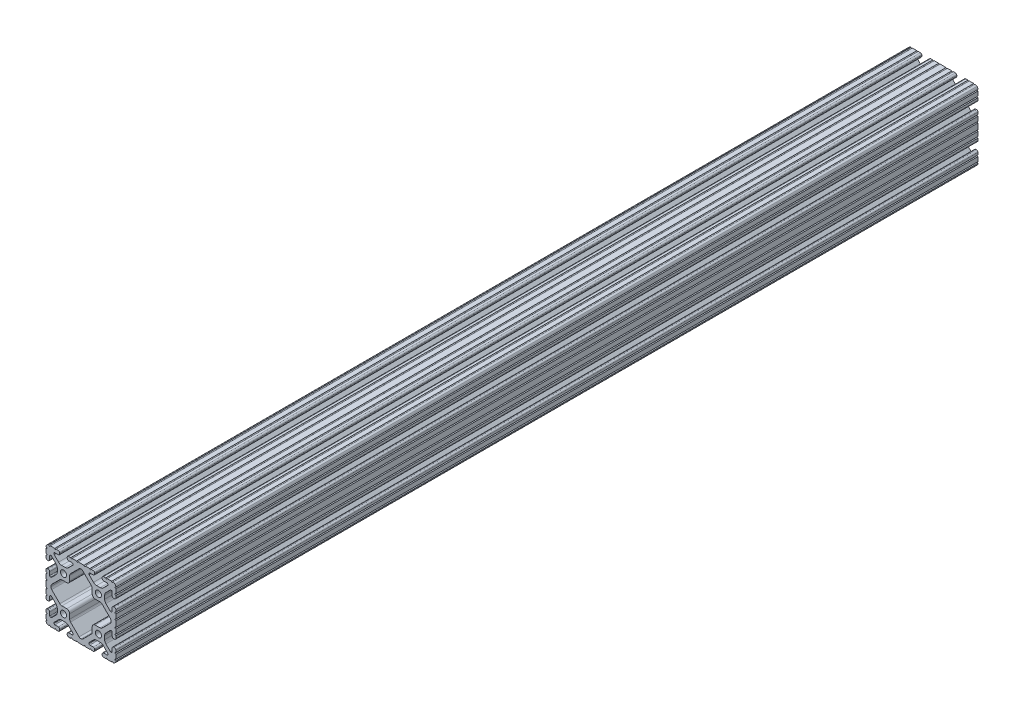
SolidWorks part; units mm, degrees
ref_plane "Front Plane" through (0, 0, 0) normal (0, 0, 1) x (1, 0, 0)
ref_plane "Top Plane" through (0, 0, 0) normal (0, 1, 0) x (1, 0, 0)
ref_plane "Right Plane" through (0, 0, 0) normal (1, 0, 0) x (0, 0, -1)
sketch "Sketch1" plane through (0, 0, 0) normal (0, 0, 1) x (1, 0, 0)
  line L0 (0, 38.1) -> (0, -38.1) construction
  line L1 (-38.1, -38.1) -> (38.1, -38.1) construction
  line L2 (-38.1, -38.1) -> (-38.1, 38.1) construction
  line L3 (-38.1, 38.1) -> (38.1, 38.1) construction
  line L4 (38.1, -38.1) -> (38.1, 38.1) construction
  line L5 (0, 38.1) -> (0, -38.1) construction
  line L6 (-38.1, 0) -> (38.1, 0) construction
  line L7 (-19.05, 19.05) -> (19.05, 19.05) construction
  line L8 (-19.05, 19.05) -> (-19.05, -19.05) construction
  line L9 (-19.05, -19.05) -> (19.05, -19.05) construction
  line L10 (19.05, 19.05) -> (19.05, -19.05) construction
  line L11 (-23.114, 38.1) -> (-23.114, -38.1) construction
  line L12 (-23.114, -38.1) -> (-14.986, 38.1) construction
  line L13 (-14.986, 38.1) -> (-14.986, -38.1) construction
  circle A0 centre (19.05, 19.05) radius 3.3274
  point P0 (0, 0)
  point P9 (0, 0)
  point P12 (-19.05, 0)
  line B0 (-11.3637, -22.8433) -> (-2.0515, -32.1555)
  line B1 (-12.2936, -15.4686) -> (-12.2936, -20.5983)
  line B2 (-20.769, -12.2936) -> (-15.4686, -12.2936)
  line B3 (-31.9021, -2.4756) -> (-23.0141, -11.3637)
  line B4 (-23.0141, 11.3637) -> (-31.9021, 2.4756)
  line B5 (-15.4686, 12.2936) -> (-20.769, 12.2936)
  line B6 (-12.2936, 20.5983) -> (-12.2936, 15.4686)
  line B7 (-2.0515, 32.1555) -> (-11.3637, 22.8433)
  line B8 (11.3637, 22.8433) -> (2.0515, 32.1555)
  line B9 (12.2936, 15.4686) -> (12.2936, 20.5983)
  line B10 (20.769, 12.2936) -> (15.4686, 12.2936)
  line B11 (31.9021, 2.4756) -> (23.0141, 11.3637)
  line B12 (23.0141, -11.3637) -> (31.9021, -2.4756)
  line B13 (15.4686, -12.2936) -> (20.769, -12.2936)
  line B14 (12.2936, -20.5983) -> (12.2936, -15.4686)
  line B15 (2.0515, -32.1555) -> (11.3637, -22.8433)
  line B16 (-4.7773, 38.1) -> (-9.6053, 38.1)
  line B17 (-11.1289, 38.1) -> (-13.4112, 38.1)
  line B18 (-14.986, 36.5252) -> (-14.986, 35.6108)
  line B19 (-13.4112, 34.036) -> (-9.652, 34.036)
  line B20 (-8.763, 33.147) -> (-8.763, 32.4935)
  line B21 (-9.0234, 31.8649) -> (-13.6907, 27.1976)
  line B22 (-17.0493, 25.8064) -> (-21.0507, 25.8064)
  line B23 (-24.4093, 27.1976) -> (-29.1002, 31.8885)
  line B24 (-29.337, 32.7207) -> (-29.337, 33.147)
  line B25 (-28.448, 34.036) -> (-24.6888, 34.036)
  line B26 (-23.114, 35.6108) -> (-23.114, 36.5252)
  line B27 (-24.6888, 38.1) -> (-27.0772, 38.1)
  line B28 (-28.6011, 38.1) -> (-33.4288, 38.1)
  line B29 (-38.1, 33.373) -> (-38.1, 28.5453)
  line B30 (-38.1, 27.0238) -> (-38.1, 24.6302)
  line B31 (-36.5252, 23.0554) -> (-35.6108, 23.0554)
  line B32 (-34.036, 24.6302) -> (-34.036, 28.448)
  line B33 (-33.147, 29.337) -> (-32.6643, 29.337)
  line B34 (-32.0357, 29.0766) -> (-27.1976, 24.2385)
  line B35 (-25.8064, 20.8799) -> (-25.8064, 17.2201)
  line B36 (-27.1976, 13.8615) -> (-31.9489, 9.1101)
  line B37 (-32.7869, 8.763) -> (-33.0603, 8.763)
  line B38 (-34.036, 9.7387) -> (-34.036, 13.4698)
  line B39 (-35.6108, 15.0446) -> (-36.5252, 15.0446)
  line B40 (-38.1, 13.4698) -> (-38.1, 11.075)
  line B41 (-38.1, 9.552) -> (-38.1, 4.7238)
  line B42 (-38.1, 3.2007) -> (-38.1, -3.2007)
  line B43 (-38.1, -4.7238) -> (-38.1, -9.552)
  line B44 (-38.1, -11.075) -> (-38.1, -13.4698)
  line B45 (-36.5252, -15.0446) -> (-35.6108, -15.0446)
  line B46 (-34.036, -13.4698) -> (-34.036, -9.7387)
  line B47 (-33.0603, -8.763) -> (-32.7869, -8.763)
  line B48 (-31.9489, -9.1101) -> (-27.1976, -13.8615)
  line B49 (-25.8064, -17.2201) -> (-25.8064, -20.8799)
  line B50 (-27.1976, -24.2385) -> (-32.0357, -29.0766)
  line B51 (-32.6643, -29.337) -> (-33.147, -29.337)
  line B52 (-34.036, -28.448) -> (-34.036, -24.6302)
  line B53 (-35.6108, -23.0554) -> (-36.5252, -23.0554)
  line B54 (-38.1, -24.6302) -> (-38.1, -27.0238)
  line B55 (-38.1, -28.5453) -> (-38.1, -33.373)
  line B56 (-33.4288, -38.1) -> (-28.6011, -38.1)
  line B57 (-27.0772, -38.1) -> (-24.6888, -38.1)
  line B58 (-23.114, -36.5252) -> (-23.114, -35.6108)
  line B59 (-24.6888, -34.036) -> (-28.448, -34.036)
  line B60 (-29.337, -33.147) -> (-29.337, -32.7207)
  line B61 (-29.1002, -31.8885) -> (-24.4093, -27.1976)
  line B62 (-21.0507, -25.8064) -> (-17.0493, -25.8064)
  line B63 (-13.6907, -27.1976) -> (-9.0234, -31.8649)
  line B64 (-8.763, -32.4935) -> (-8.763, -33.147)
  line B65 (-9.652, -34.036) -> (-13.4112, -34.036)
  line B66 (-14.986, -35.6108) -> (-14.986, -36.5252)
  line B67 (-13.4112, -38.1) -> (-11.1289, -38.1)
  line B68 (-9.6053, -38.1) -> (-4.7773, -38.1)
  line B69 (-3.2537, -38.1) -> (3.2537, -38.1)
  line B70 (4.7773, -38.1) -> (9.6053, -38.1)
  line B71 (11.1289, -38.1) -> (13.4112, -38.1)
  line B72 (14.986, -36.5252) -> (14.986, -35.6108)
  line B73 (13.4112, -34.036) -> (9.652, -34.036)
  line B74 (8.763, -33.147) -> (8.763, -32.4935)
  line B75 (9.0234, -31.8649) -> (13.6907, -27.1976)
  line B76 (17.0493, -25.8064) -> (21.0507, -25.8064)
  line B77 (24.4093, -27.1976) -> (29.1002, -31.8885)
  line B78 (29.337, -32.7207) -> (29.337, -33.147)
  line B79 (28.448, -34.036) -> (24.6888, -34.036)
  line B80 (23.114, -35.6108) -> (23.114, -36.5252)
  line B81 (24.6888, -38.1) -> (27.0772, -38.1)
  line B82 (28.6011, -38.1) -> (33.4288, -38.1)
  line B83 (38.1, -33.373) -> (38.1, -28.5453)
  line B84 (38.1, -27.0238) -> (38.1, -24.6302)
  line B85 (36.5252, -23.0554) -> (35.6108, -23.0554)
  line B86 (34.036, -24.6302) -> (34.036, -28.448)
  line B87 (33.147, -29.337) -> (32.6643, -29.337)
  line B88 (32.0357, -29.0766) -> (27.1976, -24.2385)
  line B89 (25.8064, -20.8799) -> (25.8064, -17.2201)
  line B90 (27.1976, -13.8615) -> (31.9489, -9.1101)
  line B91 (32.7869, -8.763) -> (33.0603, -8.763)
  line B92 (34.036, -9.7387) -> (34.036, -13.4698)
  line B93 (35.6108, -15.0446) -> (36.5252, -15.0446)
  line B94 (38.1, -13.4698) -> (38.1, -11.075)
  line B95 (38.1, -9.552) -> (38.1, -4.7238)
  line B96 (38.1, -3.2007) -> (38.1, 3.2007)
  line B97 (38.1, 4.7238) -> (38.1, 9.552)
  line B98 (38.1, 11.075) -> (38.1, 13.4698)
  line B99 (36.5252, 15.0446) -> (35.6108, 15.0446)
  line B100 (34.036, 13.4698) -> (34.036, 9.7387)
  line B101 (33.0603, 8.763) -> (32.7869, 8.763)
  line B102 (31.9489, 9.1101) -> (27.1976, 13.8615)
  line B103 (25.8064, 17.2201) -> (25.8064, 20.8799)
  line B104 (27.1976, 24.2385) -> (32.0357, 29.0766)
  line B105 (32.6643, 29.337) -> (33.147, 29.337)
  line B106 (34.036, 28.448) -> (34.036, 24.6302)
  line B107 (35.6108, 23.0554) -> (36.5252, 23.0554)
  line B108 (38.1, 24.6302) -> (38.1, 27.0238)
  line B109 (38.1, 28.5453) -> (38.1, 33.373)
  line B110 (33.4288, 38.1) -> (28.6011, 38.1)
  line B111 (27.0772, 38.1) -> (24.6888, 38.1)
  line B112 (23.114, 36.5252) -> (23.114, 35.6108)
  line B113 (24.6888, 34.036) -> (28.448, 34.036)
  line B114 (29.337, 33.147) -> (29.337, 32.7207)
  line B115 (29.1002, 31.8885) -> (24.4093, 27.1976)
  line B116 (21.0507, 25.8064) -> (17.0493, 25.8064)
  line B117 (13.6907, 27.1976) -> (9.0234, 31.8649)
  line B118 (8.763, 32.4935) -> (8.763, 33.147)
  line B119 (9.652, 34.036) -> (13.4112, 34.036)
  line B120 (14.986, 35.6108) -> (14.986, 36.5252)
  line B121 (13.4112, 38.1) -> (11.1289, 38.1)
  line B122 (9.6053, 38.1) -> (4.7773, 38.1)
  line B123 (3.2537, 38.1) -> (-3.2537, 38.1)
  circle B124 centre (-19.05, 19.05) radius 3.3274
  circle B125 centre (-19.05, -19.05) radius 3.3274
  circle B126 centre (19.05, -19.05) radius 3.3274
  circle B127 centre (19.05, 19.05) radius 3.3274
  arc B128 (0, -33.011) -> (2.0515, -32.1555) centre (-0.0139, -30.09) ccw
  arc B129 (-2.0515, -32.1555) -> (0, -33.011) centre (0.0139, -30.09) ccw
  arc B130 (-12.2936, -20.5983) -> (-11.3637, -22.8433) centre (-9.1186, -20.5983) ccw
  arc B131 (-12.2936, -15.4686) -> (-15.4686, -12.2936) centre (-15.4686, -15.4686) ccw
  arc B132 (-23.0141, -11.3637) -> (-20.769, -12.2936) centre (-20.769, -9.1186) ccw
  arc B133 (-32.7287, 0) -> (-31.9021, -2.4756) centre (-29.8367, -0.4102) ccw
  arc B134 (-31.9021, 2.4756) -> (-32.7287, 0) centre (-29.8367, 0.4102) ccw
  arc B135 (-20.769, 12.2936) -> (-23.0141, 11.3637) centre (-20.769, 9.1186) ccw
  arc B136 (-15.4686, 12.2936) -> (-12.2936, 15.4686) centre (-15.4686, 15.4686) ccw
  arc B137 (-11.3637, 22.8433) -> (-12.2936, 20.5983) centre (-9.1186, 20.5983) ccw
  arc B138 (0, 33.011) -> (-2.0515, 32.1555) centre (0.0139, 30.09) ccw
  arc B139 (2.0515, 32.1555) -> (0, 33.011) centre (-0.0139, 30.09) ccw
  arc B140 (12.2936, 20.5983) -> (11.3637, 22.8433) centre (9.1186, 20.5983) ccw
  arc B141 (12.2936, 15.4686) -> (15.4686, 12.2936) centre (15.4686, 15.4686) ccw
  arc B142 (23.0141, 11.3637) -> (20.769, 12.2936) centre (20.769, 9.1186) ccw
  arc B143 (32.7287, 0) -> (31.9021, 2.4756) centre (29.8367, 0.4102) ccw
  arc B144 (31.9021, -2.4756) -> (32.7287, 0) centre (29.8367, -0.4102) ccw
  arc B145 (20.769, -12.2936) -> (23.0141, -11.3637) centre (20.769, -9.1186) ccw
  arc B146 (15.4686, -12.2936) -> (12.2936, -15.4686) centre (15.4686, -15.4686) ccw
  arc B147 (11.3637, -22.8433) -> (12.2936, -20.5983) centre (9.1186, -20.5983) ccw
  arc B148 (-4.7773, 38.1) -> (-3.2537, 38.1) centre (-4.0155, 38.0824) ccw
  arc B149 (-11.1289, 38.1) -> (-9.6053, 38.1) centre (-10.3671, 38.0824) ccw
  arc B150 (-13.4112, 38.1) -> (-14.986, 36.5252) centre (-13.4112, 36.5252) ccw
  arc B151 (-14.986, 35.6108) -> (-13.4112, 34.036) centre (-13.4112, 35.6108) ccw
  arc B152 (-8.763, 33.147) -> (-9.652, 34.036) centre (-9.652, 33.147) ccw
  arc B153 (-9.0234, 31.8649) -> (-8.763, 32.4935) centre (-9.652, 32.4935) ccw
  arc B154 (-17.0493, 25.8064) -> (-13.6907, 27.1976) centre (-17.0493, 30.5562) ccw
  arc B155 (-24.4093, 27.1976) -> (-21.0507, 25.8064) centre (-21.0507, 30.5562) ccw
  arc B156 (-29.337, 32.7207) -> (-29.1002, 31.8885) centre (-28.4716, 32.5172) ccw
  arc B157 (-28.448, 34.036) -> (-29.337, 33.147) centre (-28.448, 33.147) ccw
  arc B158 (-24.6888, 34.036) -> (-23.114, 35.6108) centre (-24.6888, 35.6108) ccw
  arc B159 (-23.114, 36.5252) -> (-24.6888, 38.1) centre (-24.6888, 36.5252) ccw
  arc B160 (-28.6011, 38.1) -> (-27.0772, 38.1) centre (-27.8392, 38.0824) ccw
  arc B161 (-34.9527, 38.1) -> (-33.4288, 38.1) centre (-34.1907, 38.0824) ccw
  arc B162 (-34.9527, 38.1) -> (-37.0861, 37.1826) centre (-34.8521, 34.9266) ccw
  arc B163 (-37.0861, 37.1826) -> (-38.1, 34.8455) centre (-34.925, 34.8566) ccw
  arc B164 (-38.1, 33.373) -> (-38.1, 34.8455) centre (-37.9035, 34.1092) ccw
  arc B165 (-38.1, 27.0238) -> (-38.1, 28.5453) centre (-37.9035, 27.7845) ccw
  arc B166 (-38.1, 24.6302) -> (-36.5252, 23.0554) centre (-36.5252, 24.6302) ccw
  arc B167 (-35.6108, 23.0554) -> (-34.036, 24.6302) centre (-35.6108, 24.6302) ccw
  arc B168 (-33.147, 29.337) -> (-34.036, 28.448) centre (-33.147, 28.448) ccw
  arc B169 (-32.0357, 29.0766) -> (-32.6643, 29.337) centre (-32.6643, 28.448) ccw
  arc B170 (-25.8064, 20.8799) -> (-27.1976, 24.2385) centre (-30.5562, 20.8799) ccw
  arc B171 (-27.1976, 13.8615) -> (-25.8064, 17.2201) centre (-30.5562, 17.2201) ccw
  arc B172 (-32.7869, 8.763) -> (-31.9489, 9.1101) centre (-32.7869, 9.9481) ccw
  arc B173 (-34.036, 9.7387) -> (-33.0603, 8.763) centre (-33.0603, 9.7387) ccw
  arc B174 (-34.036, 13.4698) -> (-35.6108, 15.0446) centre (-35.6108, 13.4698) ccw
  arc B175 (-36.5252, 15.0446) -> (-38.1, 13.4698) centre (-36.5252, 13.4698) ccw
  arc B176 (-38.1, 9.552) -> (-38.1, 11.075) centre (-37.9035, 10.3135) ccw
  arc B177 (-38.1, 3.2007) -> (-38.1, 4.7238) centre (-37.9035, 3.9622) ccw
  arc B178 (-38.1, -4.7238) -> (-38.1, -3.2007) centre (-37.9035, -3.9622) ccw
  arc B179 (-38.1, -11.075) -> (-38.1, -9.552) centre (-37.9035, -10.3135) ccw
  arc B180 (-38.1, -13.4698) -> (-36.5252, -15.0446) centre (-36.5252, -13.4698) ccw
  arc B181 (-35.6108, -15.0446) -> (-34.036, -13.4698) centre (-35.6108, -13.4698) ccw
  arc B182 (-33.0603, -8.763) -> (-34.036, -9.7387) centre (-33.0603, -9.7387) ccw
  arc B183 (-31.9489, -9.1101) -> (-32.7869, -8.763) centre (-32.7869, -9.9481) ccw
  arc B184 (-25.8064, -17.2201) -> (-27.1976, -13.8615) centre (-30.5562, -17.2201) ccw
  arc B185 (-27.1976, -24.2385) -> (-25.8064, -20.8799) centre (-30.5562, -20.8799) ccw
  arc B186 (-32.6643, -29.337) -> (-32.0357, -29.0766) centre (-32.6643, -28.448) ccw
  arc B187 (-34.036, -28.448) -> (-33.147, -29.337) centre (-33.147, -28.448) ccw
  arc B188 (-34.036, -24.6302) -> (-35.6108, -23.0554) centre (-35.6108, -24.6302) ccw
  arc B189 (-36.5252, -23.0554) -> (-38.1, -24.6302) centre (-36.5252, -24.6302) ccw
  arc B190 (-38.1, -28.5453) -> (-38.1, -27.0238) centre (-37.9035, -27.7845) ccw
  arc B191 (-38.1, -34.8455) -> (-38.1, -33.373) centre (-37.9035, -34.1092) ccw
  arc B192 (-38.1, -34.8455) -> (-37.0861, -37.1826) centre (-34.925, -34.8566) ccw
  arc B193 (-37.0861, -37.1826) -> (-34.9527, -38.1) centre (-34.8521, -34.9266) ccw
  arc B194 (-33.4288, -38.1) -> (-34.9527, -38.1) centre (-34.1907, -38.0824) ccw
  arc B195 (-27.0772, -38.1) -> (-28.6011, -38.1) centre (-27.8392, -38.0824) ccw
  arc B196 (-24.6888, -38.1) -> (-23.114, -36.5252) centre (-24.6888, -36.5252) ccw
  arc B197 (-23.114, -35.6108) -> (-24.6888, -34.036) centre (-24.6888, -35.6108) ccw
  arc B198 (-29.337, -33.147) -> (-28.448, -34.036) centre (-28.448, -33.147) ccw
  arc B199 (-29.1002, -31.8885) -> (-29.337, -32.7207) centre (-28.4716, -32.5172) ccw
  arc B200 (-21.0507, -25.8064) -> (-24.4093, -27.1976) centre (-21.0507, -30.5562) ccw
  arc B201 (-13.6907, -27.1976) -> (-17.0493, -25.8064) centre (-17.0493, -30.5562) ccw
  arc B202 (-8.763, -32.4935) -> (-9.0234, -31.8649) centre (-9.652, -32.4935) ccw
  arc B203 (-9.652, -34.036) -> (-8.763, -33.147) centre (-9.652, -33.147) ccw
  arc B204 (-13.4112, -34.036) -> (-14.986, -35.6108) centre (-13.4112, -35.6108) ccw
  arc B205 (-14.986, -36.5252) -> (-13.4112, -38.1) centre (-13.4112, -36.5252) ccw
  arc B206 (-9.6053, -38.1) -> (-11.1289, -38.1) centre (-10.3671, -38.0824) ccw
  arc B207 (-3.2537, -38.1) -> (-4.7773, -38.1) centre (-4.0155, -38.0824) ccw
  arc B208 (4.7773, -38.1) -> (3.2537, -38.1) centre (4.0155, -38.0824) ccw
  arc B209 (11.1289, -38.1) -> (9.6053, -38.1) centre (10.3671, -38.0824) ccw
  arc B210 (13.4112, -38.1) -> (14.986, -36.5252) centre (13.4112, -36.5252) ccw
  arc B211 (14.986, -35.6108) -> (13.4112, -34.036) centre (13.4112, -35.6108) ccw
  arc B212 (8.763, -33.147) -> (9.652, -34.036) centre (9.652, -33.147) ccw
  arc B213 (9.0234, -31.8649) -> (8.763, -32.4935) centre (9.652, -32.4935) ccw
  arc B214 (17.0493, -25.8064) -> (13.6907, -27.1976) centre (17.0493, -30.5562) ccw
  arc B215 (24.4093, -27.1976) -> (21.0507, -25.8064) centre (21.0507, -30.5562) ccw
  arc B216 (29.337, -32.7207) -> (29.1002, -31.8885) centre (28.4716, -32.5172) ccw
  arc B217 (28.448, -34.036) -> (29.337, -33.147) centre (28.448, -33.147) ccw
  arc B218 (24.6888, -34.036) -> (23.114, -35.6108) centre (24.6888, -35.6108) ccw
  arc B219 (23.114, -36.5252) -> (24.6888, -38.1) centre (24.6888, -36.5252) ccw
  arc B220 (28.6011, -38.1) -> (27.0772, -38.1) centre (27.8392, -38.0824) ccw
  arc B221 (34.9527, -38.1) -> (33.4288, -38.1) centre (34.1907, -38.0824) ccw
  arc B222 (34.9527, -38.1) -> (37.0861, -37.1826) centre (34.8521, -34.9266) ccw
  arc B223 (37.0861, -37.1826) -> (38.1, -34.8455) centre (34.925, -34.8566) ccw
  arc B224 (38.1, -33.373) -> (38.1, -34.8455) centre (37.9035, -34.1092) ccw
  arc B225 (38.1, -27.0238) -> (38.1, -28.5453) centre (37.9035, -27.7845) ccw
  arc B226 (38.1, -24.6302) -> (36.5252, -23.0554) centre (36.5252, -24.6302) ccw
  arc B227 (35.6108, -23.0554) -> (34.036, -24.6302) centre (35.6108, -24.6302) ccw
  arc B228 (33.147, -29.337) -> (34.036, -28.448) centre (33.147, -28.448) ccw
  arc B229 (32.0357, -29.0766) -> (32.6643, -29.337) centre (32.6643, -28.448) ccw
  arc B230 (25.8064, -20.8799) -> (27.1976, -24.2385) centre (30.5562, -20.8799) ccw
  arc B231 (27.1976, -13.8615) -> (25.8064, -17.2201) centre (30.5562, -17.2201) ccw
  arc B232 (32.7869, -8.763) -> (31.9489, -9.1101) centre (32.7869, -9.9481) ccw
  arc B233 (34.036, -9.7387) -> (33.0603, -8.763) centre (33.0603, -9.7387) ccw
  arc B234 (34.036, -13.4698) -> (35.6108, -15.0446) centre (35.6108, -13.4698) ccw
  arc B235 (36.5252, -15.0446) -> (38.1, -13.4698) centre (36.5252, -13.4698) ccw
  arc B236 (38.1, -9.552) -> (38.1, -11.075) centre (37.9035, -10.3135) ccw
  arc B237 (38.1, -3.2007) -> (38.1, -4.7238) centre (37.9035, -3.9622) ccw
  arc B238 (38.1, 4.7238) -> (38.1, 3.2007) centre (37.9035, 3.9622) ccw
  arc B239 (38.1, 11.075) -> (38.1, 9.552) centre (37.9035, 10.3135) ccw
  arc B240 (38.1, 13.4698) -> (36.5252, 15.0446) centre (36.5252, 13.4698) ccw
  arc B241 (35.6108, 15.0446) -> (34.036, 13.4698) centre (35.6108, 13.4698) ccw
  arc B242 (33.0603, 8.763) -> (34.036, 9.7387) centre (33.0603, 9.7387) ccw
  arc B243 (31.9489, 9.1101) -> (32.7869, 8.763) centre (32.7869, 9.9481) ccw
  arc B244 (25.8064, 17.2201) -> (27.1976, 13.8615) centre (30.5562, 17.2201) ccw
  arc B245 (27.1976, 24.2385) -> (25.8064, 20.8799) centre (30.5562, 20.8799) ccw
  arc B246 (32.6643, 29.337) -> (32.0357, 29.0766) centre (32.6643, 28.448) ccw
  arc B247 (34.036, 28.448) -> (33.147, 29.337) centre (33.147, 28.448) ccw
  arc B248 (34.036, 24.6302) -> (35.6108, 23.0554) centre (35.6108, 24.6302) ccw
  arc B249 (36.5252, 23.0554) -> (38.1, 24.6302) centre (36.5252, 24.6302) ccw
  arc B250 (38.1, 28.5453) -> (38.1, 27.0238) centre (37.9035, 27.7845) ccw
  arc B251 (38.1, 34.8455) -> (38.1, 33.373) centre (37.9035, 34.1092) ccw
  arc B252 (38.1, 34.8455) -> (37.0861, 37.1826) centre (34.925, 34.8566) ccw
  arc B253 (37.0861, 37.1826) -> (34.9527, 38.1) centre (34.8521, 34.9266) ccw
  arc B254 (33.4288, 38.1) -> (34.9527, 38.1) centre (34.1907, 38.0824) ccw
  arc B255 (27.0772, 38.1) -> (28.6011, 38.1) centre (27.8392, 38.0824) ccw
  arc B256 (24.6888, 38.1) -> (23.114, 36.5252) centre (24.6888, 36.5252) ccw
  arc B257 (23.114, 35.6108) -> (24.6888, 34.036) centre (24.6888, 35.6108) ccw
  arc B258 (29.337, 33.147) -> (28.448, 34.036) centre (28.448, 33.147) ccw
  arc B259 (29.1002, 31.8885) -> (29.337, 32.7207) centre (28.4716, 32.5172) ccw
  arc B260 (21.0507, 25.8064) -> (24.4093, 27.1976) centre (21.0507, 30.5562) ccw
  arc B261 (13.6907, 27.1976) -> (17.0493, 25.8064) centre (17.0493, 30.5562) ccw
  arc B262 (8.763, 32.4935) -> (9.0234, 31.8649) centre (9.652, 32.4935) ccw
  arc B263 (9.652, 34.036) -> (8.763, 33.147) centre (9.652, 33.147) ccw
  arc B264 (13.4112, 34.036) -> (14.986, 35.6108) centre (13.4112, 35.6108) ccw
  arc B265 (14.986, 36.5252) -> (13.4112, 38.1) centre (13.4112, 36.5252) ccw
  arc B266 (9.6053, 38.1) -> (11.1289, 38.1) centre (10.3671, 38.0824) ccw
  arc B267 (3.2537, 38.1) -> (4.7773, 38.1) centre (4.0155, 38.0824) ccw
  dimension "Center Hole Diameter" = 6.6548
  dimension "Rail Width" = 76.2
  dimension "Rail Height" = 76.2
  dimension "T-Slot Width" = 8.128
sketch_block_instance "Block1-1"
sketch_block "Block1"
sketch "Sketch2" plane through (0, 0, 0) normal (1, 0, 0) x (0, 0, -1)
  line L0 (-469.9, 0) -> (469.9, 0) construction
  line L1 (-469.9, 38.1) -> (-469.9, -38.1) construction
  line L2 (-469.9, -38.1) -> (469.9, -38.1) construction
  line L3 (469.9, -38.1) -> (469.9, 38.1) construction
  line L4 (-368.3, 0) -> (-368.3, 38.1) construction
  line L5 (-368.3, 38.1) -> (368.3, 38.1) construction
  line L6 (368.3, 38.1) -> (368.3, 0) construction
  point P5 (368.3, 0)
  point P10 (-368.3, 0)
  dimension "D1" = 101.6
  dimension "Length" = 939.8
  dimension "D2" = 101.6
sketch "Sketch3" plane through (0, 0, 0) normal (0, 0, 1) x (1, 0, 0)
  line L0 (-11.3637, -22.8433) -> (-2.0515, -32.1555) construction
  line L1 (-12.2936, -15.4686) -> (-12.2936, -20.5983) construction
  line L2 (-20.769, -12.2936) -> (-15.4686, -12.2936) construction
  line L3 (-31.9021, -2.4756) -> (-23.0141, -11.3637) construction
  line L4 (-23.0141, 11.3637) -> (-31.9021, 2.4756) construction
  line L5 (-15.4686, 12.2936) -> (-20.769, 12.2936) construction
  line L6 (-12.2936, 20.5983) -> (-12.2936, 15.4686) construction
  line L7 (-2.0515, 32.1555) -> (-11.3637, 22.8433) construction
  line L8 (11.3637, 22.8433) -> (2.0515, 32.1555) construction
  line L9 (12.2936, 15.4686) -> (12.2936, 20.5983) construction
  line L10 (20.769, 12.2936) -> (15.4686, 12.2936) construction
  line L11 (31.9021, 2.4756) -> (23.0141, 11.3637) construction
  line L12 (23.0141, -11.3637) -> (31.9021, -2.4756) construction
  line L13 (15.4686, -12.2936) -> (20.769, -12.2936) construction
  line L14 (12.2936, -20.5983) -> (12.2936, -15.4686) construction
  line L15 (2.0515, -32.1555) -> (11.3637, -22.8433) construction
  line L16 (34.036, 28.448) -> (34.036, 24.6302) construction
  line L17 (35.6108, 23.0554) -> (36.5252, 23.0554) construction
  line L18 (38.1, 24.6302) -> (38.1, 27.0238) construction
  line L19 (38.1, 28.5453) -> (38.1, 33.373) construction
  line L20 (33.4288, 38.1) -> (28.6011, 38.1) construction
  line L21 (27.0772, 38.1) -> (24.6888, 38.1) construction
  line L22 (23.114, 36.5252) -> (23.114, 35.6108) construction
  line L23 (24.6888, 34.036) -> (28.448, 34.036) construction
  line L24 (29.337, 33.147) -> (29.337, 32.7207) construction
  line L25 (29.1002, 31.8885) -> (24.4093, 27.1976) construction
  line L26 (21.0507, 25.8064) -> (17.0493, 25.8064) construction
  line L27 (13.6907, 27.1976) -> (9.0234, 31.8649) construction
  line L28 (8.763, 32.4935) -> (8.763, 33.147) construction
  line L29 (9.652, 34.036) -> (13.4112, 34.036) construction
  line L30 (14.986, 35.6108) -> (14.986, 36.5252) construction
  line L31 (13.4112, 38.1) -> (11.1289, 38.1) construction
  line L32 (9.6053, 38.1) -> (4.7773, 38.1) construction
  line L33 (3.2537, 38.1) -> (-3.2537, 38.1) construction
  line L34 (-4.7773, 38.1) -> (-9.6053, 38.1) construction
  line L35 (-11.1289, 38.1) -> (-13.4112, 38.1) construction
  line L36 (-14.986, 36.5252) -> (-14.986, 35.6108) construction
  line L37 (-13.4112, 34.036) -> (-9.652, 34.036) construction
  line L38 (-8.763, 33.147) -> (-8.763, 32.4935) construction
  line L39 (-9.0234, 31.8649) -> (-13.6907, 27.1976) construction
  line L40 (-17.0493, 25.8064) -> (-21.0507, 25.8064) construction
  line L41 (-24.4093, 27.1976) -> (-29.1002, 31.8885) construction
  line L42 (-29.337, 32.7207) -> (-29.337, 33.147) construction
  line L43 (-28.448, 34.036) -> (-24.6888, 34.036) construction
  line L44 (-23.114, 35.6108) -> (-23.114, 36.5252) construction
  line L45 (-24.6888, 38.1) -> (-27.0772, 38.1) construction
  line L46 (-28.6011, 38.1) -> (-33.4288, 38.1) construction
  line L47 (-38.1, 33.373) -> (-38.1, 28.5453) construction
  line L48 (-38.1, 27.0238) -> (-38.1, 24.6302) construction
  line L49 (-36.5252, 23.0554) -> (-35.6108, 23.0554) construction
  line L50 (-34.036, 24.6302) -> (-34.036, 28.448) construction
  line L51 (-33.147, 29.337) -> (-32.6643, 29.337) construction
  line L52 (-32.0357, 29.0766) -> (-27.1976, 24.2385) construction
  line L53 (-25.8064, 20.8799) -> (-25.8064, 17.2201) construction
  line L54 (-27.1976, 13.8615) -> (-31.9489, 9.1101) construction
  line L55 (-32.7869, 8.763) -> (-33.0603, 8.763) construction
  line L56 (-34.036, 9.7387) -> (-34.036, 13.4698) construction
  line L57 (-35.6108, 15.0446) -> (-36.5252, 15.0446) construction
  line L58 (-38.1, 13.4698) -> (-38.1, 11.075) construction
  line L59 (-38.1, 9.552) -> (-38.1, 4.7238) construction
  line L60 (-38.1, 3.2007) -> (-38.1, -3.2007) construction
  line L61 (-38.1, -4.7238) -> (-38.1, -9.552) construction
  line L62 (-38.1, -11.075) -> (-38.1, -13.4698) construction
  line L63 (-36.5252, -15.0446) -> (-35.6108, -15.0446) construction
  line L64 (-34.036, -13.4698) -> (-34.036, -9.7387) construction
  line L65 (-33.0603, -8.763) -> (-32.7869, -8.763) construction
  line L66 (-31.9489, -9.1101) -> (-27.1976, -13.8615) construction
  line L67 (-25.8064, -17.2201) -> (-25.8064, -20.8799) construction
  line L68 (-27.1976, -24.2385) -> (-32.0357, -29.0766) construction
  line L69 (-32.6643, -29.337) -> (-33.147, -29.337) construction
  line L70 (-34.036, -28.448) -> (-34.036, -24.6302) construction
  line L71 (-35.6108, -23.0554) -> (-36.5252, -23.0554) construction
  line L72 (-38.1, -24.6302) -> (-38.1, -27.0238) construction
  line L73 (-38.1, -28.5453) -> (-38.1, -33.373) construction
  line L74 (-33.4288, -38.1) -> (-28.6011, -38.1) construction
  line L75 (-27.0772, -38.1) -> (-24.6888, -38.1) construction
  line L76 (-23.114, -36.5252) -> (-23.114, -35.6108) construction
  line L77 (-24.6888, -34.036) -> (-28.448, -34.036) construction
  line L78 (-29.337, -33.147) -> (-29.337, -32.7207) construction
  line L79 (-29.1002, -31.8885) -> (-24.4093, -27.1976) construction
  line L80 (-21.0507, -25.8064) -> (-17.0493, -25.8064) construction
  line L81 (-13.6907, -27.1976) -> (-9.0234, -31.8649) construction
  line L82 (-8.763, -32.4935) -> (-8.763, -33.147) construction
  line L83 (-9.652, -34.036) -> (-13.4112, -34.036) construction
  line L84 (-14.986, -35.6108) -> (-14.986, -36.5252) construction
  line L85 (-13.4112, -38.1) -> (-11.1289, -38.1) construction
  line L86 (-9.6053, -38.1) -> (-4.7773, -38.1) construction
  line L87 (-3.2537, -38.1) -> (3.2537, -38.1) construction
  line L88 (4.7773, -38.1) -> (9.6053, -38.1) construction
  line L89 (11.1289, -38.1) -> (13.4112, -38.1) construction
  line L90 (14.986, -36.5252) -> (14.986, -35.6108) construction
  line L91 (13.4112, -34.036) -> (9.652, -34.036) construction
  line L92 (8.763, -33.147) -> (8.763, -32.4935) construction
  line L93 (9.0234, -31.8649) -> (13.6907, -27.1976) construction
  line L94 (17.0493, -25.8064) -> (21.0507, -25.8064) construction
  line L95 (24.4093, -27.1976) -> (29.1002, -31.8885) construction
  line L96 (29.337, -32.7207) -> (29.337, -33.147) construction
  line L97 (28.448, -34.036) -> (24.6888, -34.036) construction
  line L98 (23.114, -35.6108) -> (23.114, -36.5252) construction
  line L99 (24.6888, -38.1) -> (27.0772, -38.1) construction
  line L100 (28.6011, -38.1) -> (33.4288, -38.1) construction
  line L101 (38.1, -33.373) -> (38.1, -28.5453) construction
  line L102 (38.1, -27.0238) -> (38.1, -24.6302) construction
  line L103 (36.5252, -23.0554) -> (35.6108, -23.0554) construction
  line L104 (34.036, -24.6302) -> (34.036, -28.448) construction
  line L105 (33.147, -29.337) -> (32.6643, -29.337) construction
  line L106 (32.0357, -29.0766) -> (27.1976, -24.2385) construction
  line L107 (25.8064, -20.8799) -> (25.8064, -17.2201) construction
  line L108 (27.1976, -13.8615) -> (31.9489, -9.1101) construction
  line L109 (32.7869, -8.763) -> (33.0603, -8.763) construction
  line L110 (34.036, -9.7387) -> (34.036, -13.4698) construction
  line L111 (35.6108, -15.0446) -> (36.5252, -15.0446) construction
  line L112 (38.1, -13.4698) -> (38.1, -11.075) construction
  line L113 (38.1, -9.552) -> (38.1, -4.7238) construction
  line L114 (38.1, -3.2007) -> (38.1, 3.2007) construction
  line L115 (38.1, 4.7238) -> (38.1, 9.552) construction
  line L116 (38.1, 11.075) -> (38.1, 13.4698) construction
  line L117 (36.5252, 15.0446) -> (35.6108, 15.0446) construction
  line L118 (34.036, 13.4698) -> (34.036, 9.7387) construction
  line L119 (33.0603, 8.763) -> (32.7869, 8.763) construction
  line L120 (31.9489, 9.1101) -> (27.1976, 13.8615) construction
  line L121 (25.8064, 17.2201) -> (25.8064, 20.8799) construction
  line L122 (27.1976, 24.2385) -> (32.0357, 29.0766) construction
  line L123 (32.6643, 29.337) -> (33.147, 29.337) construction
  line L124 (-11.3637, -22.8433) -> (-2.0515, -32.1555)
  line L125 (-12.2936, -15.4686) -> (-12.2936, -20.5983)
  line L126 (-20.769, -12.2936) -> (-15.4686, -12.2936)
  line L127 (-31.9021, -2.4756) -> (-23.0141, -11.3637)
  line L128 (-23.0141, 11.3637) -> (-31.9021, 2.4756)
  line L129 (-15.4686, 12.2936) -> (-20.769, 12.2936)
  line L130 (-12.2936, 20.5983) -> (-12.2936, 15.4686)
  line L131 (-2.0515, 32.1555) -> (-11.3637, 22.8433)
  line L132 (11.3637, 22.8433) -> (2.0515, 32.1555)
  line L133 (12.2936, 15.4686) -> (12.2936, 20.5983)
  line L134 (20.769, 12.2936) -> (15.4686, 12.2936)
  line L135 (31.9021, 2.4756) -> (23.0141, 11.3637)
  line L136 (23.0141, -11.3637) -> (31.9021, -2.4756)
  line L137 (15.4686, -12.2936) -> (20.769, -12.2936)
  line L138 (12.2936, -20.5983) -> (12.2936, -15.4686)
  line L139 (2.0515, -32.1555) -> (11.3637, -22.8433)
  line L140 (34.036, 28.448) -> (34.036, 24.6302)
  line L141 (35.6108, 23.0554) -> (36.5252, 23.0554)
  line L142 (38.1, 24.6302) -> (38.1, 27.0238)
  line L143 (38.1, 28.5453) -> (38.1, 33.373)
  line L144 (33.4288, 38.1) -> (28.6011, 38.1)
  line L145 (27.0772, 38.1) -> (24.6888, 38.1)
  line L146 (23.114, 36.5252) -> (23.114, 35.6108)
  line L147 (24.6888, 34.036) -> (28.448, 34.036)
  line L148 (29.337, 33.147) -> (29.337, 32.7207)
  line L149 (29.1002, 31.8885) -> (24.4093, 27.1976)
  line L150 (21.0507, 25.8064) -> (17.0493, 25.8064)
  line L151 (13.6907, 27.1976) -> (9.0234, 31.8649)
  line L152 (8.763, 32.4935) -> (8.763, 33.147)
  line L153 (9.652, 34.036) -> (13.4112, 34.036)
  line L154 (14.986, 35.6108) -> (14.986, 36.5252)
  line L155 (13.4112, 38.1) -> (11.1289, 38.1)
  line L156 (9.6053, 38.1) -> (4.7773, 38.1)
  line L157 (3.2537, 38.1) -> (-3.2537, 38.1)
  line L158 (-4.7773, 38.1) -> (-9.6053, 38.1)
  line L159 (-11.1289, 38.1) -> (-13.4112, 38.1)
  line L160 (-14.986, 36.5252) -> (-14.986, 35.6108)
  line L161 (-13.4112, 34.036) -> (-9.652, 34.036)
  line L162 (-8.763, 33.147) -> (-8.763, 32.4935)
  line L163 (-9.0234, 31.8649) -> (-13.6907, 27.1976)
  line L164 (-17.0493, 25.8064) -> (-21.0507, 25.8064)
  line L165 (-24.4093, 27.1976) -> (-29.1002, 31.8885)
  line L166 (-29.337, 32.7207) -> (-29.337, 33.147)
  line L167 (-28.448, 34.036) -> (-24.6888, 34.036)
  line L168 (-23.114, 35.6108) -> (-23.114, 36.5252)
  line L169 (-24.6888, 38.1) -> (-27.0772, 38.1)
  line L170 (-28.6011, 38.1) -> (-33.4288, 38.1)
  line L171 (-38.1, 33.373) -> (-38.1, 28.5453)
  line L172 (-38.1, 27.0238) -> (-38.1, 24.6302)
  line L173 (-36.5252, 23.0554) -> (-35.6108, 23.0554)
  line L174 (-34.036, 24.6302) -> (-34.036, 28.448)
  line L175 (-33.147, 29.337) -> (-32.6643, 29.337)
  line L176 (-32.0357, 29.0766) -> (-27.1976, 24.2385)
  line L177 (-25.8064, 20.8799) -> (-25.8064, 17.2201)
  line L178 (-27.1976, 13.8615) -> (-31.9489, 9.1101)
  line L179 (-32.7869, 8.763) -> (-33.0603, 8.763)
  line L180 (-34.036, 9.7387) -> (-34.036, 13.4698)
  line L181 (-35.6108, 15.0446) -> (-36.5252, 15.0446)
  line L182 (-38.1, 13.4698) -> (-38.1, 11.075)
  line L183 (-38.1, 9.552) -> (-38.1, 4.7238)
  line L184 (-38.1, 3.2007) -> (-38.1, -3.2007)
  line L185 (-38.1, -4.7238) -> (-38.1, -9.552)
  line L186 (-38.1, -11.075) -> (-38.1, -13.4698)
  line L187 (-36.5252, -15.0446) -> (-35.6108, -15.0446)
  line L188 (-34.036, -13.4698) -> (-34.036, -9.7387)
  line L189 (-33.0603, -8.763) -> (-32.7869, -8.763)
  line L190 (-31.9489, -9.1101) -> (-27.1976, -13.8615)
  line L191 (-25.8064, -17.2201) -> (-25.8064, -20.8799)
  line L192 (-27.1976, -24.2385) -> (-32.0357, -29.0766)
  line L193 (-32.6643, -29.337) -> (-33.147, -29.337)
  line L194 (-34.036, -28.448) -> (-34.036, -24.6302)
  line L195 (-35.6108, -23.0554) -> (-36.5252, -23.0554)
  line L196 (-38.1, -24.6302) -> (-38.1, -27.0238)
  line L197 (-38.1, -28.5453) -> (-38.1, -33.373)
  line L198 (-33.4288, -38.1) -> (-28.6011, -38.1)
  line L199 (-27.0772, -38.1) -> (-24.6888, -38.1)
  line L200 (-23.114, -36.5252) -> (-23.114, -35.6108)
  line L201 (-24.6888, -34.036) -> (-28.448, -34.036)
  line L202 (-29.337, -33.147) -> (-29.337, -32.7207)
  line L203 (-29.1002, -31.8885) -> (-24.4093, -27.1976)
  line L204 (-21.0507, -25.8064) -> (-17.0493, -25.8064)
  line L205 (-13.6907, -27.1976) -> (-9.0234, -31.8649)
  line L206 (-8.763, -32.4935) -> (-8.763, -33.147)
  line L207 (-9.652, -34.036) -> (-13.4112, -34.036)
  line L208 (-14.986, -35.6108) -> (-14.986, -36.5252)
  line L209 (-13.4112, -38.1) -> (-11.1289, -38.1)
  line L210 (-9.6053, -38.1) -> (-4.7773, -38.1)
  line L211 (-3.2537, -38.1) -> (3.2537, -38.1)
  line L212 (4.7773, -38.1) -> (9.6053, -38.1)
  line L213 (11.1289, -38.1) -> (13.4112, -38.1)
  line L214 (14.986, -36.5252) -> (14.986, -35.6108)
  line L215 (13.4112, -34.036) -> (9.652, -34.036)
  line L216 (8.763, -33.147) -> (8.763, -32.4935)
  line L217 (9.0234, -31.8649) -> (13.6907, -27.1976)
  line L218 (17.0493, -25.8064) -> (21.0507, -25.8064)
  line L219 (24.4093, -27.1976) -> (29.1002, -31.8885)
  line L220 (29.337, -32.7207) -> (29.337, -33.147)
  line L221 (28.448, -34.036) -> (24.6888, -34.036)
  line L222 (23.114, -35.6108) -> (23.114, -36.5252)
  line L223 (24.6888, -38.1) -> (27.0772, -38.1)
  line L224 (28.6011, -38.1) -> (33.4288, -38.1)
  line L225 (38.1, -33.373) -> (38.1, -28.5453)
  line L226 (38.1, -27.0238) -> (38.1, -24.6302)
  line L227 (36.5252, -23.0554) -> (35.6108, -23.0554)
  line L228 (34.036, -24.6302) -> (34.036, -28.448)
  line L229 (33.147, -29.337) -> (32.6643, -29.337)
  line L230 (32.0357, -29.0766) -> (27.1976, -24.2385)
  line L231 (25.8064, -20.8799) -> (25.8064, -17.2201)
  line L232 (27.1976, -13.8615) -> (31.9489, -9.1101)
  line L233 (32.7869, -8.763) -> (33.0603, -8.763)
  line L234 (34.036, -9.7387) -> (34.036, -13.4698)
  line L235 (35.6108, -15.0446) -> (36.5252, -15.0446)
  line L236 (38.1, -13.4698) -> (38.1, -11.075)
  line L237 (38.1, -9.552) -> (38.1, -4.7238)
  line L238 (38.1, -3.2007) -> (38.1, 3.2007)
  line L239 (38.1, 4.7238) -> (38.1, 9.552)
  line L240 (38.1, 11.075) -> (38.1, 13.4698)
  line L241 (36.5252, 15.0446) -> (35.6108, 15.0446)
  line L242 (34.036, 13.4698) -> (34.036, 9.7387)
  line L243 (33.0603, 8.763) -> (32.7869, 8.763)
  line L244 (31.9489, 9.1101) -> (27.1976, 13.8615)
  line L245 (25.8064, 17.2201) -> (25.8064, 20.8799)
  line L246 (27.1976, 24.2385) -> (32.0357, 29.0766)
  line L247 (32.6643, 29.337) -> (33.147, 29.337)
  arc A0 (-2.0515, -32.1555) -> (0, -33.011) centre (0.0139, -30.09) ccw construction
  circle A1 centre (19.05, 19.05) radius 3.3274
  circle A2 centre (19.05, 19.05) radius 3.3274
  arc A3 (-12.2936, -20.5983) -> (-11.3637, -22.8433) centre (-9.1186, -20.5983) ccw construction
  arc A4 (-12.2936, -15.4686) -> (-15.4686, -12.2936) centre (-15.4686, -15.4686) ccw construction
  arc A5 (-23.0141, -11.3637) -> (-20.769, -12.2936) centre (-20.769, -9.1186) ccw construction
  arc A6 (-32.7287, 0) -> (-31.9021, -2.4756) centre (-29.8367, -0.4102) ccw construction
  arc A7 (-31.9021, 2.4756) -> (-32.7287, 0) centre (-29.8367, 0.4102) ccw construction
  arc A8 (-20.769, 12.2936) -> (-23.0141, 11.3637) centre (-20.769, 9.1186) ccw construction
  arc A9 (-15.4686, 12.2936) -> (-12.2936, 15.4686) centre (-15.4686, 15.4686) ccw construction
  arc A10 (-11.3637, 22.8433) -> (-12.2936, 20.5983) centre (-9.1186, 20.5983) ccw construction
  arc A11 (0, 33.011) -> (-2.0515, 32.1555) centre (0.0139, 30.09) ccw construction
  arc A12 (2.0515, 32.1555) -> (0, 33.011) centre (-0.0139, 30.09) ccw construction
  arc A13 (12.2936, 20.5983) -> (11.3637, 22.8433) centre (9.1186, 20.5983) ccw construction
  arc A14 (12.2936, 15.4686) -> (15.4686, 12.2936) centre (15.4686, 15.4686) ccw construction
  arc A15 (23.0141, 11.3637) -> (20.769, 12.2936) centre (20.769, 9.1186) ccw construction
  arc A16 (32.7287, 0) -> (31.9021, 2.4756) centre (29.8367, 0.4102) ccw construction
  arc A17 (31.9021, -2.4756) -> (32.7287, 0) centre (29.8367, -0.4102) ccw construction
  arc A18 (20.769, -12.2936) -> (23.0141, -11.3637) centre (20.769, -9.1186) ccw construction
  arc A19 (15.4686, -12.2936) -> (12.2936, -15.4686) centre (15.4686, -15.4686) ccw construction
  arc A20 (11.3637, -22.8433) -> (12.2936, -20.5983) centre (9.1186, -20.5983) ccw construction
  arc A21 (0, -33.011) -> (2.0515, -32.1555) centre (-0.0139, -30.09) ccw construction
  circle A22 centre (-19.05, 19.05) radius 3.3274 construction
  circle A23 centre (19.05, -19.05) radius 3.3274 construction
  circle A24 centre (-19.05, -19.05) radius 3.3274 construction
  circle A25 centre (19.05, 19.05) radius 3.3274 construction
  arc A26 (34.036, 24.6302) -> (35.6108, 23.0554) centre (35.6108, 24.6302) ccw construction
  arc A27 (36.5252, 23.0554) -> (38.1, 24.6302) centre (36.5252, 24.6302) ccw construction
  arc A28 (38.1, 28.5453) -> (38.1, 27.0238) centre (37.9035, 27.7845) ccw construction
  arc A29 (38.1, 34.8455) -> (38.1, 33.373) centre (37.9035, 34.1092) ccw construction
  arc A30 (38.1, 34.8455) -> (37.0861, 37.1826) centre (34.925, 34.8566) ccw construction
  arc A31 (37.0861, 37.1826) -> (34.9527, 38.1) centre (34.8521, 34.9266) ccw construction
  arc A32 (33.4288, 38.1) -> (34.9527, 38.1) centre (34.1907, 38.0824) ccw construction
  arc A33 (27.0772, 38.1) -> (28.6011, 38.1) centre (27.8392, 38.0824) ccw construction
  arc A34 (24.6888, 38.1) -> (23.114, 36.5252) centre (24.6888, 36.5252) ccw construction
  arc A35 (23.114, 35.6108) -> (24.6888, 34.036) centre (24.6888, 35.6108) ccw construction
  arc A36 (29.337, 33.147) -> (28.448, 34.036) centre (28.448, 33.147) ccw construction
  arc A37 (29.1002, 31.8885) -> (29.337, 32.7207) centre (28.4716, 32.5172) ccw construction
  arc A38 (21.0507, 25.8064) -> (24.4093, 27.1976) centre (21.0507, 30.5562) ccw construction
  arc A39 (13.6907, 27.1976) -> (17.0493, 25.8064) centre (17.0493, 30.5562) ccw construction
  arc A40 (8.763, 32.4935) -> (9.0234, 31.8649) centre (9.652, 32.4935) ccw construction
  arc A41 (9.652, 34.036) -> (8.763, 33.147) centre (9.652, 33.147) ccw construction
  arc A42 (13.4112, 34.036) -> (14.986, 35.6108) centre (13.4112, 35.6108) ccw construction
  arc A43 (14.986, 36.5252) -> (13.4112, 38.1) centre (13.4112, 36.5252) ccw construction
  arc A44 (9.6053, 38.1) -> (11.1289, 38.1) centre (10.3671, 38.0824) ccw construction
  arc A45 (3.2537, 38.1) -> (4.7773, 38.1) centre (4.0155, 38.0824) ccw construction
  arc A46 (-4.7773, 38.1) -> (-3.2537, 38.1) centre (-4.0155, 38.0824) ccw construction
  arc A47 (-11.1289, 38.1) -> (-9.6053, 38.1) centre (-10.3671, 38.0824) ccw construction
  arc A48 (-13.4112, 38.1) -> (-14.986, 36.5252) centre (-13.4112, 36.5252) ccw construction
  arc A49 (-14.986, 35.6108) -> (-13.4112, 34.036) centre (-13.4112, 35.6108) ccw construction
  arc A50 (-8.763, 33.147) -> (-9.652, 34.036) centre (-9.652, 33.147) ccw construction
  arc A51 (-9.0234, 31.8649) -> (-8.763, 32.4935) centre (-9.652, 32.4935) ccw construction
  arc A52 (-17.0493, 25.8064) -> (-13.6907, 27.1976) centre (-17.0493, 30.5562) ccw construction
  arc A53 (-24.4093, 27.1976) -> (-21.0507, 25.8064) centre (-21.0507, 30.5562) ccw construction
  arc A54 (-29.337, 32.7207) -> (-29.1002, 31.8885) centre (-28.4716, 32.5172) ccw construction
  arc A55 (-28.448, 34.036) -> (-29.337, 33.147) centre (-28.448, 33.147) ccw construction
  arc A56 (-24.6888, 34.036) -> (-23.114, 35.6108) centre (-24.6888, 35.6108) ccw construction
  arc A57 (-23.114, 36.5252) -> (-24.6888, 38.1) centre (-24.6888, 36.5252) ccw construction
  arc A58 (-28.6011, 38.1) -> (-27.0772, 38.1) centre (-27.8392, 38.0824) ccw construction
  arc A59 (-34.9527, 38.1) -> (-33.4288, 38.1) centre (-34.1907, 38.0824) ccw construction
  arc A60 (-34.9527, 38.1) -> (-37.0861, 37.1826) centre (-34.8521, 34.9266) ccw construction
  arc A61 (-37.0861, 37.1826) -> (-38.1, 34.8455) centre (-34.925, 34.8566) ccw construction
  arc A62 (-38.1, 33.373) -> (-38.1, 34.8455) centre (-37.9035, 34.1092) ccw construction
  arc A63 (-38.1, 27.0238) -> (-38.1, 28.5453) centre (-37.9035, 27.7845) ccw construction
  arc A64 (-38.1, 24.6302) -> (-36.5252, 23.0554) centre (-36.5252, 24.6302) ccw construction
  arc A65 (-35.6108, 23.0554) -> (-34.036, 24.6302) centre (-35.6108, 24.6302) ccw construction
  arc A66 (-33.147, 29.337) -> (-34.036, 28.448) centre (-33.147, 28.448) ccw construction
  arc A67 (-32.0357, 29.0766) -> (-32.6643, 29.337) centre (-32.6643, 28.448) ccw construction
  arc A68 (-25.8064, 20.8799) -> (-27.1976, 24.2385) centre (-30.5562, 20.8799) ccw construction
  arc A69 (-27.1976, 13.8615) -> (-25.8064, 17.2201) centre (-30.5562, 17.2201) ccw construction
  arc A70 (-32.7869, 8.763) -> (-31.9489, 9.1101) centre (-32.7869, 9.9481) ccw construction
  arc A71 (-34.036, 9.7387) -> (-33.0603, 8.763) centre (-33.0603, 9.7387) ccw construction
  arc A72 (-34.036, 13.4698) -> (-35.6108, 15.0446) centre (-35.6108, 13.4698) ccw construction
  arc A73 (-36.5252, 15.0446) -> (-38.1, 13.4698) centre (-36.5252, 13.4698) ccw construction
  arc A74 (-38.1, 9.552) -> (-38.1, 11.075) centre (-37.9035, 10.3135) ccw construction
  arc A75 (-38.1, 3.2007) -> (-38.1, 4.7238) centre (-37.9035, 3.9622) ccw construction
  arc A76 (-38.1, -4.7238) -> (-38.1, -3.2007) centre (-37.9035, -3.9622) ccw construction
  arc A77 (-38.1, -11.075) -> (-38.1, -9.552) centre (-37.9035, -10.3135) ccw construction
  arc A78 (-38.1, -13.4698) -> (-36.5252, -15.0446) centre (-36.5252, -13.4698) ccw construction
  arc A79 (-35.6108, -15.0446) -> (-34.036, -13.4698) centre (-35.6108, -13.4698) ccw construction
  arc A80 (-33.0603, -8.763) -> (-34.036, -9.7387) centre (-33.0603, -9.7387) ccw construction
  arc A81 (-31.9489, -9.1101) -> (-32.7869, -8.763) centre (-32.7869, -9.9481) ccw construction
  arc A82 (-25.8064, -17.2201) -> (-27.1976, -13.8615) centre (-30.5562, -17.2201) ccw construction
  arc A83 (-27.1976, -24.2385) -> (-25.8064, -20.8799) centre (-30.5562, -20.8799) ccw construction
  arc A84 (-32.6643, -29.337) -> (-32.0357, -29.0766) centre (-32.6643, -28.448) ccw construction
  arc A85 (-34.036, -28.448) -> (-33.147, -29.337) centre (-33.147, -28.448) ccw construction
  arc A86 (-34.036, -24.6302) -> (-35.6108, -23.0554) centre (-35.6108, -24.6302) ccw construction
  arc A87 (-36.5252, -23.0554) -> (-38.1, -24.6302) centre (-36.5252, -24.6302) ccw construction
  arc A88 (-38.1, -28.5453) -> (-38.1, -27.0238) centre (-37.9035, -27.7845) ccw construction
  arc A89 (-38.1, -34.8455) -> (-38.1, -33.373) centre (-37.9035, -34.1092) ccw construction
  arc A90 (-38.1, -34.8455) -> (-37.0861, -37.1826) centre (-34.925, -34.8566) ccw construction
  arc A91 (-37.0861, -37.1826) -> (-34.9527, -38.1) centre (-34.8521, -34.9266) ccw construction
  arc A92 (-33.4288, -38.1) -> (-34.9527, -38.1) centre (-34.1907, -38.0824) ccw construction
  arc A93 (-27.0772, -38.1) -> (-28.6011, -38.1) centre (-27.8392, -38.0824) ccw construction
  arc A94 (-24.6888, -38.1) -> (-23.114, -36.5252) centre (-24.6888, -36.5252) ccw construction
  arc A95 (-23.114, -35.6108) -> (-24.6888, -34.036) centre (-24.6888, -35.6108) ccw construction
  arc A96 (-29.337, -33.147) -> (-28.448, -34.036) centre (-28.448, -33.147) ccw construction
  arc A97 (-29.1002, -31.8885) -> (-29.337, -32.7207) centre (-28.4716, -32.5172) ccw construction
  arc A98 (-21.0507, -25.8064) -> (-24.4093, -27.1976) centre (-21.0507, -30.5562) ccw construction
  arc A99 (-13.6907, -27.1976) -> (-17.0493, -25.8064) centre (-17.0493, -30.5562) ccw construction
  arc A100 (-8.763, -32.4935) -> (-9.0234, -31.8649) centre (-9.652, -32.4935) ccw construction
  arc A101 (-9.652, -34.036) -> (-8.763, -33.147) centre (-9.652, -33.147) ccw construction
  arc A102 (-13.4112, -34.036) -> (-14.986, -35.6108) centre (-13.4112, -35.6108) ccw construction
  arc A103 (-14.986, -36.5252) -> (-13.4112, -38.1) centre (-13.4112, -36.5252) ccw construction
  arc A104 (-9.6053, -38.1) -> (-11.1289, -38.1) centre (-10.3671, -38.0824) ccw construction
  arc A105 (-3.2537, -38.1) -> (-4.7773, -38.1) centre (-4.0155, -38.0824) ccw construction
  arc A106 (4.7773, -38.1) -> (3.2537, -38.1) centre (4.0155, -38.0824) ccw construction
  arc A107 (11.1289, -38.1) -> (9.6053, -38.1) centre (10.3671, -38.0824) ccw construction
  arc A108 (13.4112, -38.1) -> (14.986, -36.5252) centre (13.4112, -36.5252) ccw construction
  arc A109 (14.986, -35.6108) -> (13.4112, -34.036) centre (13.4112, -35.6108) ccw construction
  arc A110 (8.763, -33.147) -> (9.652, -34.036) centre (9.652, -33.147) ccw construction
  arc A111 (9.0234, -31.8649) -> (8.763, -32.4935) centre (9.652, -32.4935) ccw construction
  arc A112 (17.0493, -25.8064) -> (13.6907, -27.1976) centre (17.0493, -30.5562) ccw construction
  arc A113 (24.4093, -27.1976) -> (21.0507, -25.8064) centre (21.0507, -30.5562) ccw construction
  arc A114 (29.337, -32.7207) -> (29.1002, -31.8885) centre (28.4716, -32.5172) ccw construction
  arc A115 (28.448, -34.036) -> (29.337, -33.147) centre (28.448, -33.147) ccw construction
  arc A116 (24.6888, -34.036) -> (23.114, -35.6108) centre (24.6888, -35.6108) ccw construction
  arc A117 (23.114, -36.5252) -> (24.6888, -38.1) centre (24.6888, -36.5252) ccw construction
  arc A118 (28.6011, -38.1) -> (27.0772, -38.1) centre (27.8392, -38.0824) ccw construction
  arc A119 (34.9527, -38.1) -> (33.4288, -38.1) centre (34.1907, -38.0824) ccw construction
  arc A120 (34.9527, -38.1) -> (37.0861, -37.1826) centre (34.8521, -34.9266) ccw construction
  arc A121 (37.0861, -37.1826) -> (38.1, -34.8455) centre (34.925, -34.8566) ccw construction
  arc A122 (38.1, -33.373) -> (38.1, -34.8455) centre (37.9035, -34.1092) ccw construction
  arc A123 (38.1, -27.0238) -> (38.1, -28.5453) centre (37.9035, -27.7845) ccw construction
  arc A124 (38.1, -24.6302) -> (36.5252, -23.0554) centre (36.5252, -24.6302) ccw construction
  arc A125 (35.6108, -23.0554) -> (34.036, -24.6302) centre (35.6108, -24.6302) ccw construction
  arc A126 (33.147, -29.337) -> (34.036, -28.448) centre (33.147, -28.448) ccw construction
  arc A127 (32.0357, -29.0766) -> (32.6643, -29.337) centre (32.6643, -28.448) ccw construction
  arc A128 (25.8064, -20.8799) -> (27.1976, -24.2385) centre (30.5562, -20.8799) ccw construction
  arc A129 (27.1976, -13.8615) -> (25.8064, -17.2201) centre (30.5562, -17.2201) ccw construction
  arc A130 (32.7869, -8.763) -> (31.9489, -9.1101) centre (32.7869, -9.9481) ccw construction
  arc A131 (34.036, -9.7387) -> (33.0603, -8.763) centre (33.0603, -9.7387) ccw construction
  arc A132 (34.036, -13.4698) -> (35.6108, -15.0446) centre (35.6108, -13.4698) ccw construction
  arc A133 (36.5252, -15.0446) -> (38.1, -13.4698) centre (36.5252, -13.4698) ccw construction
  arc A134 (38.1, -9.552) -> (38.1, -11.075) centre (37.9035, -10.3135) ccw construction
  arc A135 (38.1, -3.2007) -> (38.1, -4.7238) centre (37.9035, -3.9622) ccw construction
  arc A136 (38.1, 4.7238) -> (38.1, 3.2007) centre (37.9035, 3.9622) ccw construction
  arc A137 (38.1, 11.075) -> (38.1, 9.552) centre (37.9035, 10.3135) ccw construction
  arc A138 (38.1, 13.4698) -> (36.5252, 15.0446) centre (36.5252, 13.4698) ccw construction
  arc A139 (35.6108, 15.0446) -> (34.036, 13.4698) centre (35.6108, 13.4698) ccw construction
  arc A140 (33.0603, 8.763) -> (34.036, 9.7387) centre (33.0603, 9.7387) ccw construction
  arc A141 (31.9489, 9.1101) -> (32.7869, 8.763) centre (32.7869, 9.9481) ccw construction
  arc A142 (25.8064, 17.2201) -> (27.1976, 13.8615) centre (30.5562, 17.2201) ccw construction
  arc A143 (27.1976, 24.2385) -> (25.8064, 20.8799) centre (30.5562, 20.8799) ccw construction
  arc A144 (32.6643, 29.337) -> (32.0357, 29.0766) centre (32.6643, 28.448) ccw construction
  arc A145 (34.036, 28.448) -> (33.147, 29.337) centre (33.147, 28.448) ccw construction
  arc A146 (-2.0515, -32.1555) -> (0, -33.011) centre (0.0139, -30.09) ccw
  arc A147 (-12.2936, -20.5983) -> (-11.3637, -22.8433) centre (-9.1186, -20.5983) ccw
  arc A148 (-12.2936, -15.4686) -> (-15.4686, -12.2936) centre (-15.4686, -15.4686) ccw
  arc A149 (-23.0141, -11.3637) -> (-20.769, -12.2936) centre (-20.769, -9.1186) ccw
  arc A150 (-32.7287, 0) -> (-31.9021, -2.4756) centre (-29.8367, -0.4102) ccw
  arc A151 (-31.9021, 2.4756) -> (-32.7287, 0) centre (-29.8367, 0.4102) ccw
  arc A152 (-20.769, 12.2936) -> (-23.0141, 11.3637) centre (-20.769, 9.1186) ccw
  arc A153 (-15.4686, 12.2936) -> (-12.2936, 15.4686) centre (-15.4686, 15.4686) ccw
  arc A154 (-11.3637, 22.8433) -> (-12.2936, 20.5983) centre (-9.1186, 20.5983) ccw
  arc A155 (0, 33.011) -> (-2.0515, 32.1555) centre (0.0139, 30.09) ccw
  arc A156 (2.0515, 32.1555) -> (0, 33.011) centre (-0.0139, 30.09) ccw
  arc A157 (12.2936, 20.5983) -> (11.3637, 22.8433) centre (9.1186, 20.5983) ccw
  arc A158 (12.2936, 15.4686) -> (15.4686, 12.2936) centre (15.4686, 15.4686) ccw
  arc A159 (23.0141, 11.3637) -> (20.769, 12.2936) centre (20.769, 9.1186) ccw
  arc A160 (32.7287, 0) -> (31.9021, 2.4756) centre (29.8367, 0.4102) ccw
  arc A161 (31.9021, -2.4756) -> (32.7287, 0) centre (29.8367, -0.4102) ccw
  arc A162 (20.769, -12.2936) -> (23.0141, -11.3637) centre (20.769, -9.1186) ccw
  arc A163 (15.4686, -12.2936) -> (12.2936, -15.4686) centre (15.4686, -15.4686) ccw
  arc A164 (11.3637, -22.8433) -> (12.2936, -20.5983) centre (9.1186, -20.5983) ccw
  arc A165 (0, -33.011) -> (2.0515, -32.1555) centre (-0.0139, -30.09) ccw
  circle A166 centre (-19.05, 19.05) radius 3.3274
  circle A167 centre (19.05, -19.05) radius 3.3274
  circle A168 centre (-19.05, -19.05) radius 3.3274
  circle A169 centre (19.05, 19.05) radius 3.3274
  arc A170 (34.036, 24.6302) -> (35.6108, 23.0554) centre (35.6108, 24.6302) ccw
  arc A171 (36.5252, 23.0554) -> (38.1, 24.6302) centre (36.5252, 24.6302) ccw
  arc A172 (38.1, 28.5453) -> (38.1, 27.0238) centre (37.9035, 27.7845) ccw
  arc A173 (38.1, 34.8455) -> (38.1, 33.373) centre (37.9035, 34.1092) ccw
  arc A174 (38.1, 34.8455) -> (37.0861, 37.1826) centre (34.925, 34.8566) ccw
  arc A175 (37.0861, 37.1826) -> (34.9527, 38.1) centre (34.8521, 34.9266) ccw
  arc A176 (33.4288, 38.1) -> (34.9527, 38.1) centre (34.1907, 38.0824) ccw
  arc A177 (27.0772, 38.1) -> (28.6011, 38.1) centre (27.8392, 38.0824) ccw
  arc A178 (24.6888, 38.1) -> (23.114, 36.5252) centre (24.6888, 36.5252) ccw
  arc A179 (23.114, 35.6108) -> (24.6888, 34.036) centre (24.6888, 35.6108) ccw
  arc A180 (29.337, 33.147) -> (28.448, 34.036) centre (28.448, 33.147) ccw
  arc A181 (29.1002, 31.8885) -> (29.337, 32.7207) centre (28.4716, 32.5172) ccw
  arc A182 (21.0507, 25.8064) -> (24.4093, 27.1976) centre (21.0507, 30.5562) ccw
  arc A183 (13.6907, 27.1976) -> (17.0493, 25.8064) centre (17.0493, 30.5562) ccw
  arc A184 (8.763, 32.4935) -> (9.0234, 31.8649) centre (9.652, 32.4935) ccw
  arc A185 (9.652, 34.036) -> (8.763, 33.147) centre (9.652, 33.147) ccw
  arc A186 (13.4112, 34.036) -> (14.986, 35.6108) centre (13.4112, 35.6108) ccw
  arc A187 (14.986, 36.5252) -> (13.4112, 38.1) centre (13.4112, 36.5252) ccw
  arc A188 (9.6053, 38.1) -> (11.1289, 38.1) centre (10.3671, 38.0824) ccw
  arc A189 (3.2537, 38.1) -> (4.7773, 38.1) centre (4.0155, 38.0824) ccw
  arc A190 (-4.7773, 38.1) -> (-3.2537, 38.1) centre (-4.0155, 38.0824) ccw
  arc A191 (-11.1289, 38.1) -> (-9.6053, 38.1) centre (-10.3671, 38.0824) ccw
  arc A192 (-13.4112, 38.1) -> (-14.986, 36.5252) centre (-13.4112, 36.5252) ccw
  arc A193 (-14.986, 35.6108) -> (-13.4112, 34.036) centre (-13.4112, 35.6108) ccw
  arc A194 (-8.763, 33.147) -> (-9.652, 34.036) centre (-9.652, 33.147) ccw
  arc A195 (-9.0234, 31.8649) -> (-8.763, 32.4935) centre (-9.652, 32.4935) ccw
  arc A196 (-17.0493, 25.8064) -> (-13.6907, 27.1976) centre (-17.0493, 30.5562) ccw
  arc A197 (-24.4093, 27.1976) -> (-21.0507, 25.8064) centre (-21.0507, 30.5562) ccw
  arc A198 (-29.337, 32.7207) -> (-29.1002, 31.8885) centre (-28.4716, 32.5172) ccw
  arc A199 (-28.448, 34.036) -> (-29.337, 33.147) centre (-28.448, 33.147) ccw
  arc A200 (-24.6888, 34.036) -> (-23.114, 35.6108) centre (-24.6888, 35.6108) ccw
  arc A201 (-23.114, 36.5252) -> (-24.6888, 38.1) centre (-24.6888, 36.5252) ccw
  arc A202 (-28.6011, 38.1) -> (-27.0772, 38.1) centre (-27.8392, 38.0824) ccw
  arc A203 (-34.9527, 38.1) -> (-33.4288, 38.1) centre (-34.1907, 38.0824) ccw
  arc A204 (-34.9527, 38.1) -> (-37.0861, 37.1826) centre (-34.8521, 34.9266) ccw
  arc A205 (-37.0861, 37.1826) -> (-38.1, 34.8455) centre (-34.925, 34.8566) ccw
  arc A206 (-38.1, 33.373) -> (-38.1, 34.8455) centre (-37.9035, 34.1092) ccw
  arc A207 (-38.1, 27.0238) -> (-38.1, 28.5453) centre (-37.9035, 27.7845) ccw
  arc A208 (-38.1, 24.6302) -> (-36.5252, 23.0554) centre (-36.5252, 24.6302) ccw
  arc A209 (-35.6108, 23.0554) -> (-34.036, 24.6302) centre (-35.6108, 24.6302) ccw
  arc A210 (-33.147, 29.337) -> (-34.036, 28.448) centre (-33.147, 28.448) ccw
  arc A211 (-32.0357, 29.0766) -> (-32.6643, 29.337) centre (-32.6643, 28.448) ccw
  arc A212 (-25.8064, 20.8799) -> (-27.1976, 24.2385) centre (-30.5562, 20.8799) ccw
  arc A213 (-27.1976, 13.8615) -> (-25.8064, 17.2201) centre (-30.5562, 17.2201) ccw
  arc A214 (-32.7869, 8.763) -> (-31.9489, 9.1101) centre (-32.7869, 9.9481) ccw
  arc A215 (-34.036, 9.7387) -> (-33.0603, 8.763) centre (-33.0603, 9.7387) ccw
  arc A216 (-34.036, 13.4698) -> (-35.6108, 15.0446) centre (-35.6108, 13.4698) ccw
  arc A217 (-36.5252, 15.0446) -> (-38.1, 13.4698) centre (-36.5252, 13.4698) ccw
  arc A218 (-38.1, 9.552) -> (-38.1, 11.075) centre (-37.9035, 10.3135) ccw
  arc A219 (-38.1, 3.2007) -> (-38.1, 4.7238) centre (-37.9035, 3.9622) ccw
  arc A220 (-38.1, -4.7238) -> (-38.1, -3.2007) centre (-37.9035, -3.9622) ccw
  arc A221 (-38.1, -11.075) -> (-38.1, -9.552) centre (-37.9035, -10.3135) ccw
  arc A222 (-38.1, -13.4698) -> (-36.5252, -15.0446) centre (-36.5252, -13.4698) ccw
  arc A223 (-35.6108, -15.0446) -> (-34.036, -13.4698) centre (-35.6108, -13.4698) ccw
  arc A224 (-33.0603, -8.763) -> (-34.036, -9.7387) centre (-33.0603, -9.7387) ccw
  arc A225 (-31.9489, -9.1101) -> (-32.7869, -8.763) centre (-32.7869, -9.9481) ccw
  arc A226 (-25.8064, -17.2201) -> (-27.1976, -13.8615) centre (-30.5562, -17.2201) ccw
  arc A227 (-27.1976, -24.2385) -> (-25.8064, -20.8799) centre (-30.5562, -20.8799) ccw
  arc A228 (-32.6643, -29.337) -> (-32.0357, -29.0766) centre (-32.6643, -28.448) ccw
  arc A229 (-34.036, -28.448) -> (-33.147, -29.337) centre (-33.147, -28.448) ccw
  arc A230 (-34.036, -24.6302) -> (-35.6108, -23.0554) centre (-35.6108, -24.6302) ccw
  arc A231 (-36.5252, -23.0554) -> (-38.1, -24.6302) centre (-36.5252, -24.6302) ccw
  arc A232 (-38.1, -28.5453) -> (-38.1, -27.0238) centre (-37.9035, -27.7845) ccw
  arc A233 (-38.1, -34.8455) -> (-38.1, -33.373) centre (-37.9035, -34.1092) ccw
  arc A234 (-38.1, -34.8455) -> (-37.0861, -37.1826) centre (-34.925, -34.8566) ccw
  arc A235 (-37.0861, -37.1826) -> (-34.9527, -38.1) centre (-34.8521, -34.9266) ccw
  arc A236 (-33.4288, -38.1) -> (-34.9527, -38.1) centre (-34.1907, -38.0824) ccw
  arc A237 (-27.0772, -38.1) -> (-28.6011, -38.1) centre (-27.8392, -38.0824) ccw
  arc A238 (-24.6888, -38.1) -> (-23.114, -36.5252) centre (-24.6888, -36.5252) ccw
  arc A239 (-23.114, -35.6108) -> (-24.6888, -34.036) centre (-24.6888, -35.6108) ccw
  arc A240 (-29.337, -33.147) -> (-28.448, -34.036) centre (-28.448, -33.147) ccw
  arc A241 (-29.1002, -31.8885) -> (-29.337, -32.7207) centre (-28.4716, -32.5172) ccw
  arc A242 (-21.0507, -25.8064) -> (-24.4093, -27.1976) centre (-21.0507, -30.5562) ccw
  arc A243 (-13.6907, -27.1976) -> (-17.0493, -25.8064) centre (-17.0493, -30.5562) ccw
  arc A244 (-8.763, -32.4935) -> (-9.0234, -31.8649) centre (-9.652, -32.4935) ccw
  arc A245 (-9.652, -34.036) -> (-8.763, -33.147) centre (-9.652, -33.147) ccw
  arc A246 (-13.4112, -34.036) -> (-14.986, -35.6108) centre (-13.4112, -35.6108) ccw
  arc A247 (-14.986, -36.5252) -> (-13.4112, -38.1) centre (-13.4112, -36.5252) ccw
  arc A248 (-9.6053, -38.1) -> (-11.1289, -38.1) centre (-10.3671, -38.0824) ccw
  arc A249 (-3.2537, -38.1) -> (-4.7773, -38.1) centre (-4.0155, -38.0824) ccw
  arc A250 (4.7773, -38.1) -> (3.2537, -38.1) centre (4.0155, -38.0824) ccw
  arc A251 (11.1289, -38.1) -> (9.6053, -38.1) centre (10.3671, -38.0824) ccw
  arc A252 (13.4112, -38.1) -> (14.986, -36.5252) centre (13.4112, -36.5252) ccw
  arc A253 (14.986, -35.6108) -> (13.4112, -34.036) centre (13.4112, -35.6108) ccw
  arc A254 (8.763, -33.147) -> (9.652, -34.036) centre (9.652, -33.147) ccw
  arc A255 (9.0234, -31.8649) -> (8.763, -32.4935) centre (9.652, -32.4935) ccw
  arc A256 (17.0493, -25.8064) -> (13.6907, -27.1976) centre (17.0493, -30.5562) ccw
  arc A257 (24.4093, -27.1976) -> (21.0507, -25.8064) centre (21.0507, -30.5562) ccw
  arc A258 (29.337, -32.7207) -> (29.1002, -31.8885) centre (28.4716, -32.5172) ccw
  arc A259 (28.448, -34.036) -> (29.337, -33.147) centre (28.448, -33.147) ccw
  arc A260 (24.6888, -34.036) -> (23.114, -35.6108) centre (24.6888, -35.6108) ccw
  arc A261 (23.114, -36.5252) -> (24.6888, -38.1) centre (24.6888, -36.5252) ccw
  arc A262 (28.6011, -38.1) -> (27.0772, -38.1) centre (27.8392, -38.0824) ccw
  arc A263 (34.9527, -38.1) -> (33.4288, -38.1) centre (34.1907, -38.0824) ccw
  arc A264 (34.9527, -38.1) -> (37.0861, -37.1826) centre (34.8521, -34.9266) ccw
  arc A265 (37.0861, -37.1826) -> (38.1, -34.8455) centre (34.925, -34.8566) ccw
  arc A266 (38.1, -33.373) -> (38.1, -34.8455) centre (37.9035, -34.1092) ccw
  arc A267 (38.1, -27.0238) -> (38.1, -28.5453) centre (37.9035, -27.7845) ccw
  arc A268 (38.1, -24.6302) -> (36.5252, -23.0554) centre (36.5252, -24.6302) ccw
  arc A269 (35.6108, -23.0554) -> (34.036, -24.6302) centre (35.6108, -24.6302) ccw
  arc A270 (33.147, -29.337) -> (34.036, -28.448) centre (33.147, -28.448) ccw
  arc A271 (32.0357, -29.0766) -> (32.6643, -29.337) centre (32.6643, -28.448) ccw
  arc A272 (25.8064, -20.8799) -> (27.1976, -24.2385) centre (30.5562, -20.8799) ccw
  arc A273 (27.1976, -13.8615) -> (25.8064, -17.2201) centre (30.5562, -17.2201) ccw
  arc A274 (32.7869, -8.763) -> (31.9489, -9.1101) centre (32.7869, -9.9481) ccw
  arc A275 (34.036, -9.7387) -> (33.0603, -8.763) centre (33.0603, -9.7387) ccw
  arc A276 (34.036, -13.4698) -> (35.6108, -15.0446) centre (35.6108, -13.4698) ccw
  arc A277 (36.5252, -15.0446) -> (38.1, -13.4698) centre (36.5252, -13.4698) ccw
  arc A278 (38.1, -9.552) -> (38.1, -11.075) centre (37.9035, -10.3135) ccw
  arc A279 (38.1, -3.2007) -> (38.1, -4.7238) centre (37.9035, -3.9622) ccw
  arc A280 (38.1, 4.7238) -> (38.1, 3.2007) centre (37.9035, 3.9622) ccw
  arc A281 (38.1, 11.075) -> (38.1, 9.552) centre (37.9035, 10.3135) ccw
  arc A282 (38.1, 13.4698) -> (36.5252, 15.0446) centre (36.5252, 13.4698) ccw
  arc A283 (35.6108, 15.0446) -> (34.036, 13.4698) centre (35.6108, 13.4698) ccw
  arc A284 (33.0603, 8.763) -> (34.036, 9.7387) centre (33.0603, 9.7387) ccw
  arc A285 (31.9489, 9.1101) -> (32.7869, 8.763) centre (32.7869, 9.9481) ccw
  arc A286 (25.8064, 17.2201) -> (27.1976, 13.8615) centre (30.5562, 17.2201) ccw
  arc A287 (27.1976, 24.2385) -> (25.8064, 20.8799) centre (30.5562, 20.8799) ccw
  arc A288 (32.6643, 29.337) -> (32.0357, 29.0766) centre (32.6643, 28.448) ccw
  arc A289 (34.036, 28.448) -> (33.147, 29.337) centre (33.147, 28.448) ccw
  dimension "D1" = 0
extrude "Boss-Extrude1" add sketch "Sketch3" along normal up to vertex (469.9 mm away) and the other way up to vertex (469.9 mm away) contours A289 L140 A170 L141 A171 L142 A172 L143 A173 A174 A175 A176 L144 A177 L145 A178 L146 A179 L147 A180 L148 A181 L149 A182 L150 A183 L151 A184 L152 A185 L153 A186 L154 A187 L155 A188 L156 A189 L157 A190 L158 A191 L159 A192 L160 A193 L161 A194 L162 A195 L163 region at (34.5376, 29.8386, 0) up to point (0, 0, 469.9) other way up to point (0, 0, -469.9)
